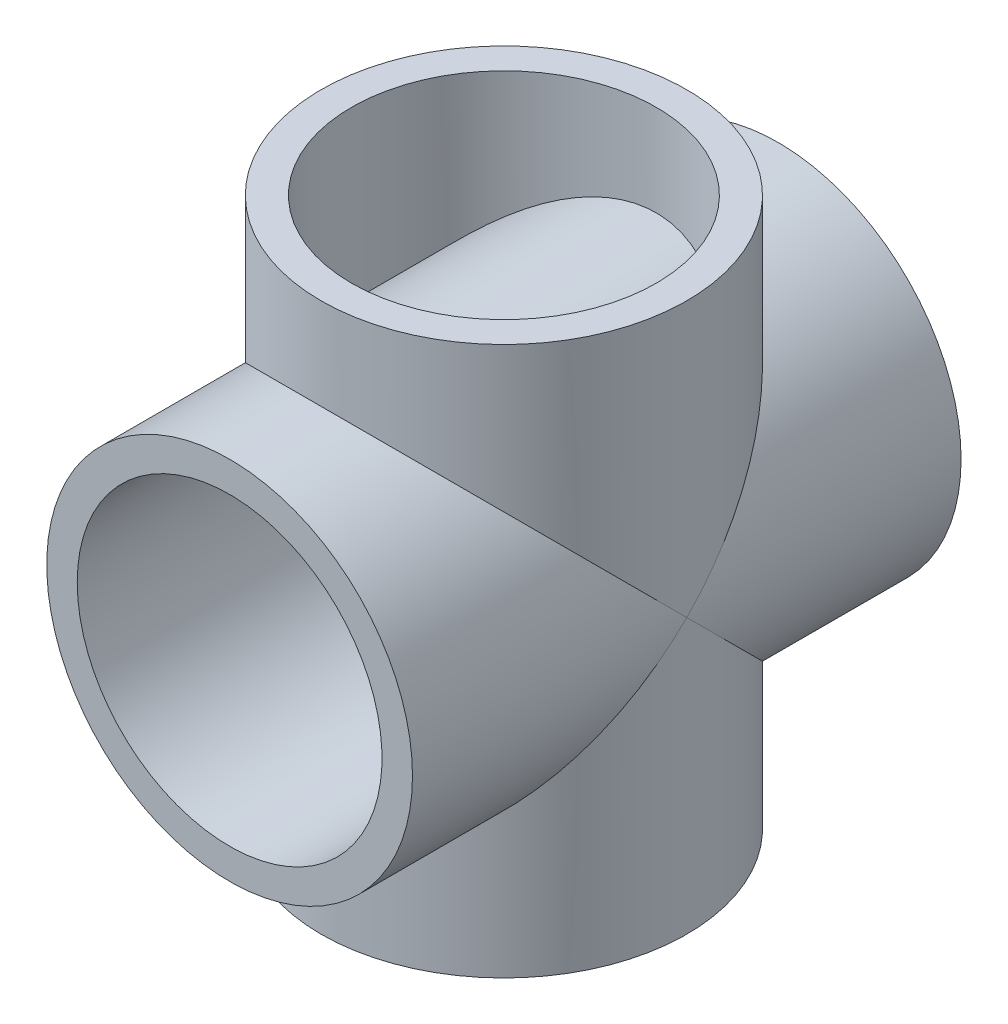
SolidWorks part; units mm, degrees
ref_plane "Front Plane" through (0, 0, 0) normal (0, 0, 1) x (1, 0, 0)
ref_plane "Top Plane" through (0, 0, 0) normal (0, 1, 0) x (1, 0, 0)
ref_plane "Right Plane" through (0, 0, 0) normal (1, 0, 0) x (0, 0, -1)
sketch "Sketch1" plane through (0, 0, 0) normal (0, 1, 0) x (1, 0, 0)
  circle A0 centre (0, 0) radius 6
  circle A1 centre (0, 0) radius 5
  dimension "D1" = 10
  dimension "D2" = 12
extrude "Boss-Extrude1" add sketch "Sketch1" along normal blind 9 and the other way blind 9
sketch "Sketch2" plane through (0, 0, 0) normal (0, 0, 1) x (1, 0, 0)
  circle A0 centre (0, 0) radius 6
  dimension "D2" = 12
extrude "Boss-Extrude2" add sketch "Sketch2" along normal blind 9 and the other way blind 9
sketch "Sketch3" plane through (0, 0, -9) normal (0, 0, -1) x (-1, 0, 0)
  circle A0 centre (0, 0) radius 5
  dimension "D1" = 10
extrude "Cut-Extrude1" cut sketch "Sketch3" against normal through all
